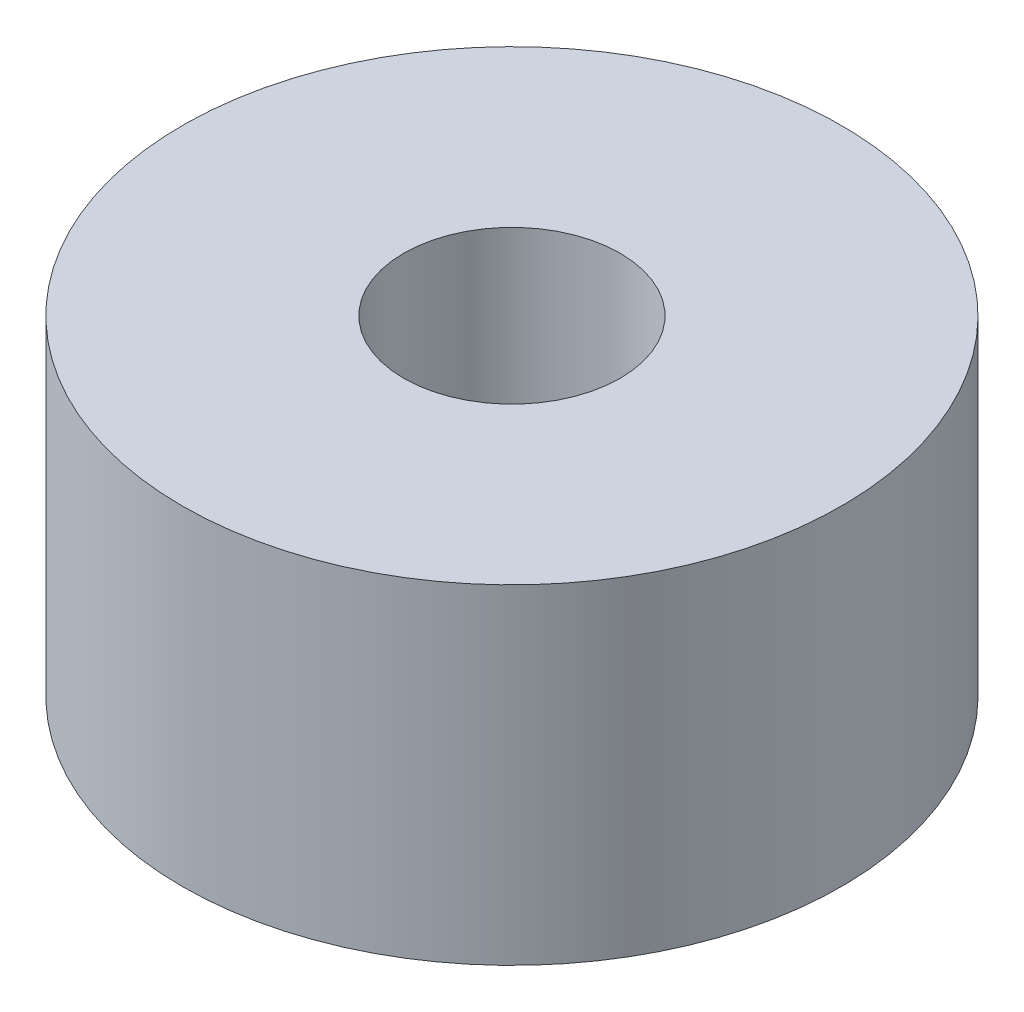
SolidWorks part; units mm, degrees
ref_plane "Front Plane" through (0, 0, 0) normal (0, 0, 1) x (1, 0, 0)
ref_plane "Top Plane" through (0, 0, 0) normal (0, 1, 0) x (1, 0, 0)
ref_plane "Right Plane" through (0, 0, 0) normal (1, 0, 0) x (0, 0, -1)
sketch "Sketch1" plane through (0, 0, 0) normal (0, 1, 0) x (1, 0, 0)
  circle A0 centre (0, 0) radius 350
  circle A1 centre (0, 0) radius 115
  dimension "D1" = 700
  dimension "D2" = 230
extrude "Boss-Extrude1" add sketch "Sketch1" against normal blind 350 contours A0 | A1
ref_axis "Axis1" through (0, -350, 0) along (0, 1, 0)
sketch "Sketch2" plane through (0, 0, 0) normal (0, 1, 0) x (1, 0, 0)
  point P0 (-240, 0)
  point P1 (240, 0)
  dimension "D1" = 240
  dimension "D2" = 240
  dimension "D3" = 0
ref_axis "Axis2" through (-240, 0, 0) along (0, -1, 0)
ref_axis "Axis3" through (240, 0, 0) along (0, -1, 0)
